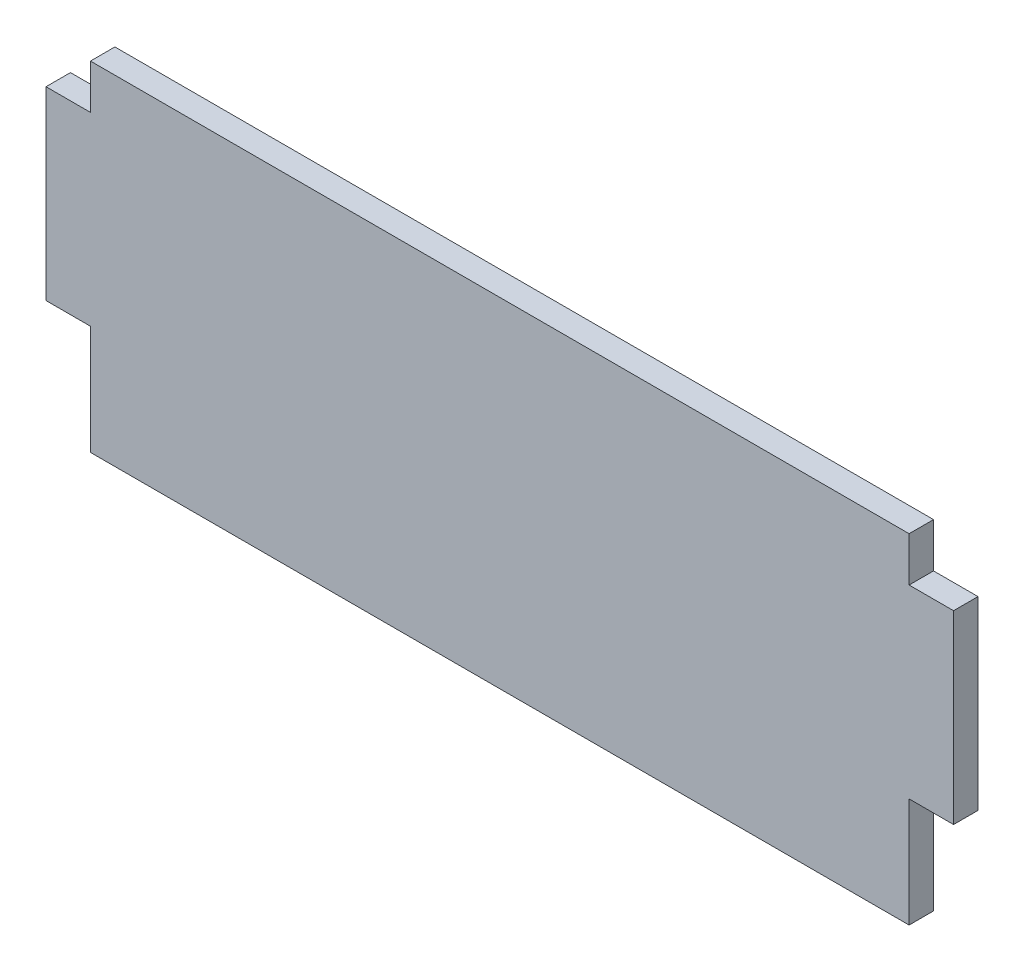
SolidWorks part; units mm, degrees
ref_plane "Front Plane" through (0, 0, 0) normal (0, 0, 1) x (1, 0, 0)
ref_plane "Top Plane" through (0, 0, 0) normal (0, 1, 0) x (1, 0, 0)
ref_plane "Right Plane" through (0, 0, 0) normal (1, 0, 0) x (0, 0, -1)
sketch "Sketch1" plane through (0, 0, 0) normal (0, 0, 1) x (1, 0, 0)
  line L0 (3.048, 84.963) -> (0, 84.963) construction
  line L1 (3.048, 84.963) -> (3.048, 72.263) construction
  line L2 (3.048, 72.263) -> (0, 72.263) construction
  line L3 (3.048, 84.963) -> (0, 84.963)
  line L4 (3.048, 84.963) -> (3.048, 72.263)
  line L5 (3.048, 72.263) -> (0, 72.263)
  line L6 (-59.182, 72.263) -> (-56.134, 72.263) construction
  line L7 (-59.182, 84.963) -> (-56.134, 84.963) construction
  line L8 (-59.182, 84.963) -> (-59.182, 72.263) construction
  line L9 (-59.182, 72.263) -> (-56.134, 72.263)
  line L10 (-59.182, 84.963) -> (-56.134, 84.963)
  line L11 (-59.182, 84.963) -> (-59.182, 72.263)
  line L12 (-56.134, 84.963) -> (-56.134, 88.011)
  line L13 (-56.134, 88.011) -> (0, 88.011)
  line L14 (0, 88.011) -> (0, 84.963)
  line L15 (0, 72.263) -> (0, 64.77)
  line L16 (0, 64.77) -> (-56.134, 64.77)
  line L17 (-56.134, 64.77) -> (-56.134, 72.263)
extrude "Boss-Extrude1" add sketch "Sketch1" along normal blind 1.6764
